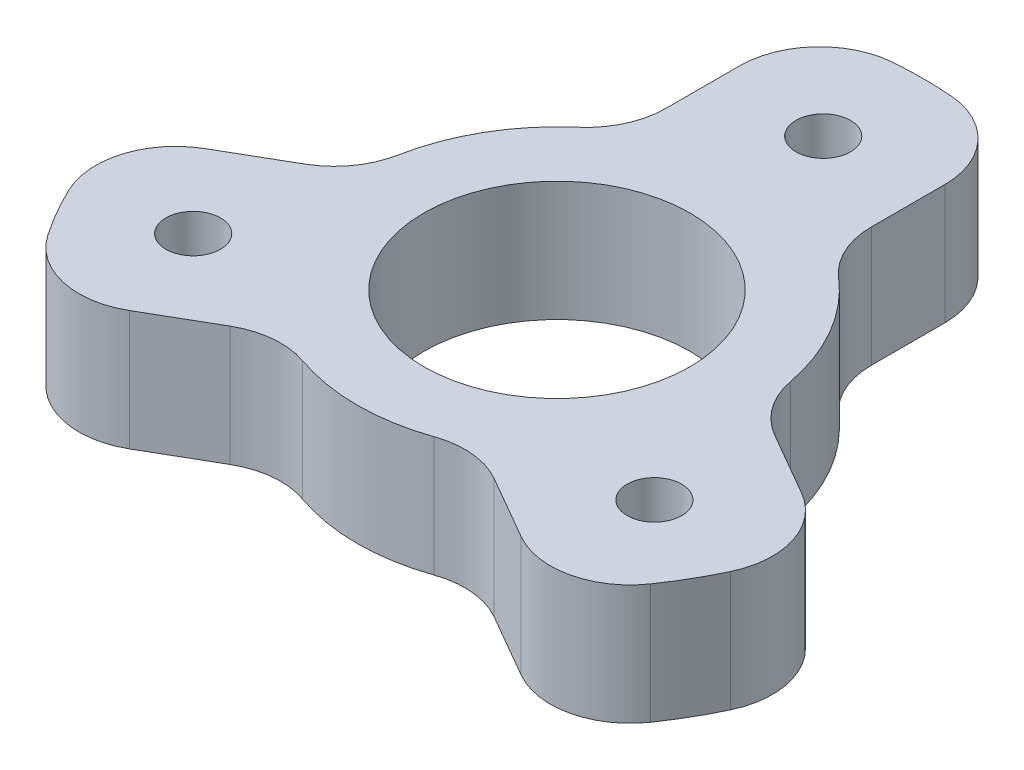
SolidWorks part; units mm, degrees
material "ABS"
ref_plane "前视基准面" through (0, 0, 0) normal (0, 0, 1) x (1, 0, 0)
ref_plane "上视基准面" through (0, 0, 0) normal (0, 1, 0) x (1, 0, 0)
ref_plane "右视基准面" through (0, 0, 0) normal (1, 0, 0) x (0, 0, -1)
sketch "草图1" plane through (0, 0, 0) normal (0, 1, 0) x (1, 0, 0)
  line L0 (14.7042, -17.395) -> (9.9179, -14.6317)
  line L1 (22.4166, -4.0367) -> (17.6303, -1.2733)
  line L2 (-7.7125, 21.4317) -> (-7.7125, 15.905)
  line L3 (7.7125, 21.4317) -> (7.7125, 15.905)
  line L4 (-22.4166, -4.0367) -> (-17.6303, -1.2733)
  line L5 (-14.7042, -17.395) -> (-9.9179, -14.6317)
  arc A0 (-24.8352, -11.8094) -> (-22.6449, -15.6032) centre (0, 0) ccw
  circle A1 centre (0, 0) radius 20 construction
  circle A2 centre (0, 20) radius 2.05
  circle A3 centre (17.3205, -10) radius 2.05
  circle A4 centre (-17.3205, -10) radius 2.05
  circle A5 centre (0, 0) radius 10
  arc A6 (-9.7946, 11.3607) -> (-14.736, 2.802) centre (0, 0) ccw
  arc A7 (2.1904, 27.4126) -> (-2.1904, 27.4126) centre (0, 0) ccw
  arc A8 (22.6449, -15.6032) -> (24.8352, -11.8094) centre (0, 0) ccw
  arc A9 (-4.9413, -14.1627) -> (4.9413, -14.1627) centre (0, 0) ccw
  arc A10 (14.736, 2.802) -> (9.7946, 11.3607) centre (0, 0) ccw
  arc A11 (-9.7946, 11.3607) -> (-7.7125, 15.905) centre (-13.7125, 15.905) ccw
  arc A12 (9.7946, 11.3607) -> (7.7125, 15.905) centre (13.7125, 15.905) cw
  arc A13 (17.6303, -1.2733) -> (14.736, 2.802) centre (20.6303, 3.9229) cw
  arc A14 (9.9179, -14.6317) -> (4.9413, -14.1627) centre (6.9179, -19.8278) ccw
  arc A15 (-4.9413, -14.1627) -> (-9.9179, -14.6317) centre (-6.9179, -19.8278) ccw
  arc A16 (-17.6303, -1.2733) -> (-14.736, 2.802) centre (-20.6303, 3.9229) ccw
  arc A17 (-24.8352, -11.8094) -> (-22.4166, -4.0367) centre (-19.4166, -9.2328) cw
  arc A18 (-22.6449, -15.6032) -> (-14.7042, -17.395) centre (-17.7042, -12.1989) ccw
  arc A19 (22.6449, -15.6032) -> (14.7042, -17.395) centre (17.7042, -12.1989) cw
  arc A20 (24.8352, -11.8094) -> (22.4166, -4.0367) centre (19.4166, -9.2328) ccw
  arc A21 (7.7125, 21.4317) -> (2.1904, 27.4126) centre (1.7125, 21.4317) ccw
  arc A22 (-7.7125, 21.4317) -> (-2.1904, 27.4126) centre (-1.7125, 21.4317) cw
  point P13 (0, 0)
  point P27 (0, 0)
  point P46 (7.7125, 26.3964)
  dimension "D1" = 55
  dimension "D2" = 40
  dimension "D3" = 4.1
  dimension "D5" = 20
  dimension "D7" = 30
  dimension "D8" = 6
  dimension "D6" = 3
  dimension "D4" = 3
extrude "凸台-拉伸1" add sketch "草图1" along normal blind 9
